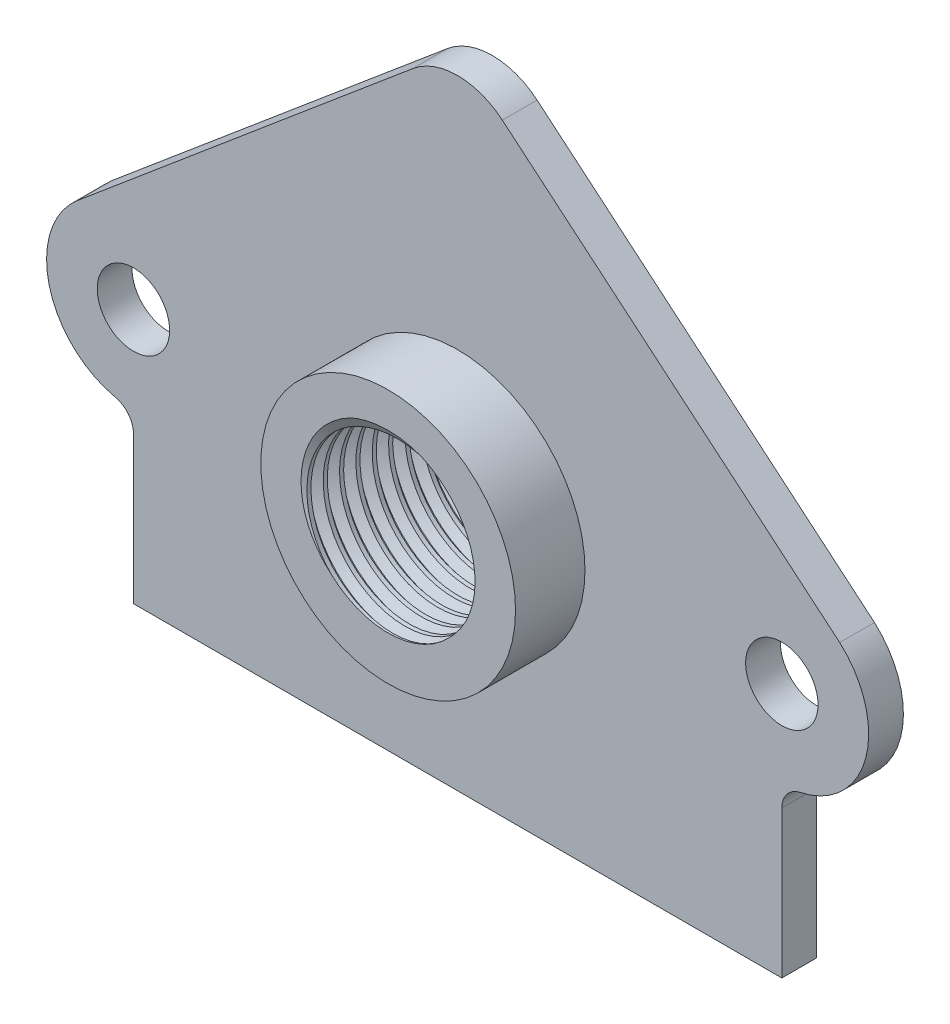
SolidWorks part; units mm, degrees
ref_plane "Front Plane" through (0, 0, 0) normal (0, 0, 1) x (1, 0, 0)
ref_plane "Top Plane" through (0, 0, 0) normal (0, 1, 0) x (1, 0, 0)
ref_plane "Right Plane" through (0, 0, 0) normal (1, 0, 0) x (0, 0, -1)
sketch "Sketch2" plane through (0, 0, 0) normal (0, 0, 1) x (1, 0, 0)
  line L0 (-3.8611, 30.0926) -> (-32.8264, 5.7407)
  line L1 (3.8611, 30.0926) -> (32.9978, 5.5921)
  line L2 (-28, -7.5) -> (-28, -22)
  line L3 (28, -7.5) -> (28, -22)
  line L4 (-28, -22) -> (28, -22)
  circle A1 centre (-28, 0) radius 3.125
  circle A2 centre (28, 0) radius 3.125
  arc A3 (3.8619, 30.0919) -> (-3.8611, 30.0926) centre (0, 25.5) ccw
  arc A4 (-1.3989, -10.9107) -> (0, -11) centre (0, 0) ccw
  arc A5 (-32.8264, 5.7407) -> (-28, -7.5) centre (-28, 0) ccw
  arc A6 (28, -7.5) -> (32.6516, 5.8833) centre (28, 0) ccw
  circle A7 centre (0, 0) radius 7.2
  circle A8 centre (0, 0) radius 11
  dimension "D4" = 6.25
  dimension "D5" = 6.25
  dimension "D6" = 12
  dimension "D9" = 22
  dimension "D10" = 15
  dimension "D11" = 15
  dimension "D12" = 14.4
  dimension "D13" = 22
  dimension "D2" = 28
  dimension "D3" = 28
  dimension "D7" = 25.5
  dimension "D8" = 28
  dimension "D14" = 22
  dimension "D15" = 22
extrude "Boss-Extrude2" add sketch "Sketch2" along normal blind 3 contours A8 A6 L1 A3 L0 A5 A4 A1 A2 | A4 A8 region at (0, 30.611, 0) region at (-7.0612, 8.0244, 0)
sketch "Sketch5" plane through (0, 0, 0) normal (0, 0, -1) x (-1, 0, 0)
  circle A2 centre (0, 0) radius 11
  circle A4 centre (0, 0) radius 7.2
  dimension "D1" = 14.4
  dimension "D2" = 22
extrude "Boss-Extrude3" add sketch "Sketch5" along normal blind 6 contours A2 | A4
sketch "Sketch6" plane through (0, 0, 3) normal (0, 0, 1) x (1, 0, 0)
  circle A0 centre (0, 0) radius 11
  circle A4 centre (0, 0) radius 7.2
  dimension "D1" = 22
  dimension "D2" = 14.4
extrude "Boss-Extrude4" add sketch "Sketch6" along normal blind 6
ref_axis "Axis1" through (0, 0, 9) along (0, 0, -1)
fillet "Fillet1" radius 2 2 edges at (28, -7.5, 1.5) (-28, -7.5, 1.5)
thread "Thread1" pitch 1.4111 method cut trim with start face yes trim with end face yes profile "Thread Profile1" start angle 0, offset 1.41, length 0, pitch 1.4111, diameter 14.4
ref_plane "Plane1" through (7.2, 0, -7.41) normal (0, -1, 0) x (1, 0, 0)
sketch "Thread Profile1" plane through (7.2, 0, -7.41) normal (0, -1, 0) x (1, 0, 0)
  line L0 (0, 0) -> (0, 1.4111) construction
  line L1 (0, 0) -> (0.7638, 0.441)
  line L2 (0.7638, 0.441) -> (0.7638, 0.6174)
  line L3 (0.7638, 0.6174) -> (0, 1.0583)
  line L4 (0.7638, 0.5292) -> (0, 0.5292) construction
  line L11 (0, 0) -> (0, 1.0583)
  point P2 (0, 0)
  dimension "Pitch" = 1.4111
  dimension "Profile_Angle" = 60
  dimension "Profile_Land" = 0.1764
  dimension "Profile_Height" = 0.7638
